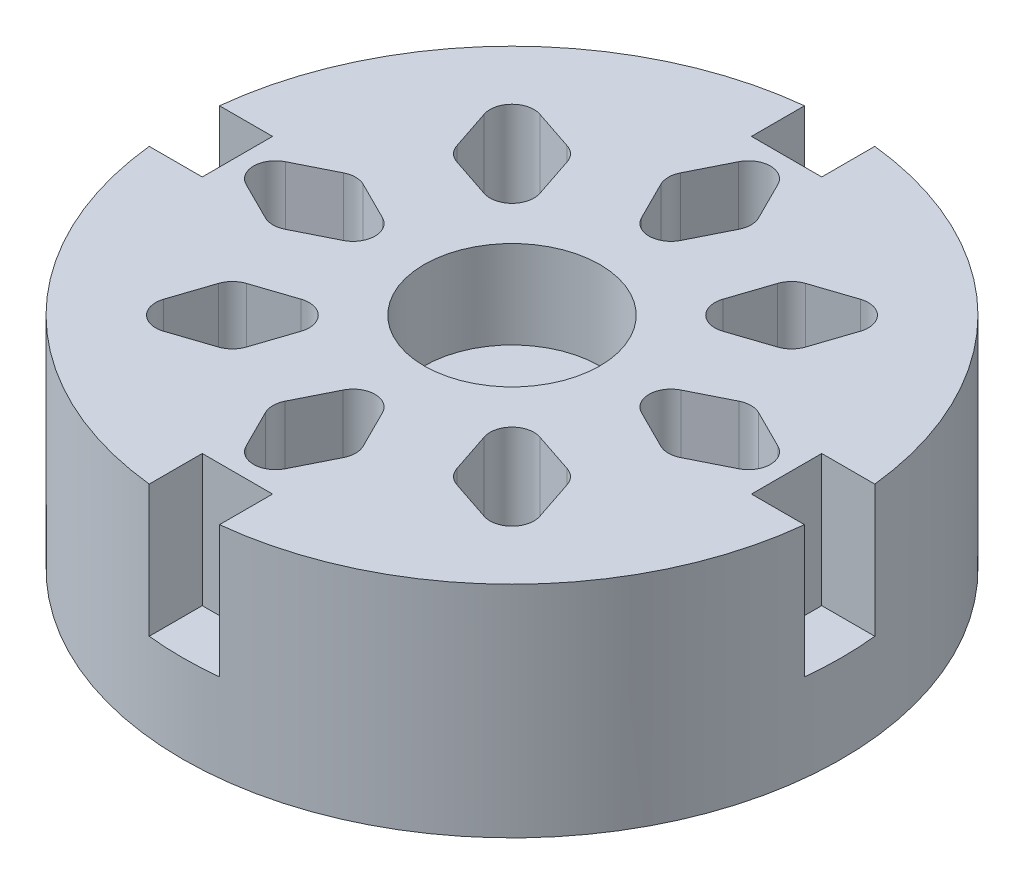
SolidWorks part; units mm, degrees
material "PET"
ref_plane "Спереди" through (0, 0, 0) normal (0, 0, 1) x (1, 0, 0)
ref_plane "Сверху" through (0, 0, 0) normal (0, 1, 0) x (1, 0, 0)
ref_plane "Справа" through (0, 0, 0) normal (1, 0, 0) x (0, 0, -1)
sketch "Эскиз1" plane through (0, 0, 0) normal (0, 1, 0) x (1, 0, 0)
  circle A0 centre (0, 0) radius 4
  circle A1 centre (0, 0) radius 15
  dimension "D1" = 8
  dimension "D2" = 30
extrude "Бобышка-Вытянуть1" add sketch "Эскиз1" along normal blind 10
sketch "Эскиз4" plane through (0, 0, 0) normal (0, -1, 0) x (1, 0, 0)
  circle A16 centre (0, 0) radius 15
  circle A32 centre (0, 0) radius 15
  dimension "D1" = 0
extrude "Бобышка-Вытянуть2" add sketch "Эскиз4" against normal blind 6
sketch "Эскиз5" plane through (0, 6, 0) normal (0, 1, 0) x (1, 0, 0)
  circle A0 centre (0, 0) radius 1.6
  dimension "D1" = 3.2
extrude "Вырез-Вытянуть2" cut sketch "Эскиз5" against normal through all both and the other way through all
sketch "Эскиз6" plane through (0, 0, 0) normal (0, -1, 0) x (1, 0, 0)
  line L0 (0, 0) -> (-5, 0) construction
  line L1 (-6.7889, 0.8944) -> (-8.5528, 1.7764)
  line L2 (-9.4472, 1.7764) -> (-11.2111, 0.8944)
  line L3 (-11.2111, -0.8944) -> (-9.4472, -1.7764)
  line L4 (-8.5528, -1.7764) -> (-6.7889, -0.8944)
  line L5 (-13, 0) -> (-5, 0) construction
  line L6 (-9, 2) -> (-9, -2) construction
  line L7 (-4.168, 5.4329) -> (-4.7916, 7.3038)
  line L8 (-5.4241, 7.9363) -> (-7.295, 8.5599)
  line L9 (-8.5599, 7.295) -> (-7.9363, 5.4241)
  line L10 (-7.3038, 4.7916) -> (-5.4329, 4.168)
  line L11 (0, 0) -> (-3.5355, 3.5355) construction
  line L12 (-9.1924, 9.1924) -> (-3.5355, 3.5355) construction
  line L13 (-4.9497, 7.7782) -> (-7.7782, 4.9497) construction
  line L14 (0.8944, 6.7889) -> (1.7764, 8.5528)
  line L15 (1.7764, 9.4472) -> (0.8944, 11.2111)
  line L16 (-0.8944, 11.2111) -> (-1.7764, 9.4472)
  line L17 (-1.7764, 8.5528) -> (-0.8944, 6.7889)
  line L18 (0, 0) -> (0, 5) construction
  line L19 (0, 13) -> (0, 5) construction
  line L20 (2, 9) -> (-2, 9) construction
  line L21 (5.4329, 4.168) -> (7.3038, 4.7916)
  line L22 (7.9363, 5.4241) -> (8.5599, 7.295)
  line L23 (7.295, 8.5599) -> (5.4241, 7.9363)
  line L24 (4.7916, 7.3038) -> (4.168, 5.4329)
  line L25 (0, 0) -> (3.5355, 3.5355) construction
  line L26 (9.1924, 9.1924) -> (3.5355, 3.5355) construction
  line L27 (7.7782, 4.9497) -> (4.9497, 7.7782) construction
  line L28 (6.7889, -0.8944) -> (8.5528, -1.7764)
  line L29 (9.4472, -1.7764) -> (11.2111, -0.8944)
  line L30 (11.2111, 0.8944) -> (9.4472, 1.7764)
  line L31 (8.5528, 1.7764) -> (6.7889, 0.8944)
  line L32 (0, 0) -> (5, 0) construction
  line L33 (13, 0) -> (5, 0) construction
  line L34 (9, -2) -> (9, 2) construction
  line L35 (4.168, -5.4329) -> (4.7916, -7.3038)
  line L36 (5.4241, -7.9363) -> (7.295, -8.5599)
  line L37 (8.5599, -7.295) -> (7.9363, -5.4241)
  line L38 (7.3038, -4.7916) -> (5.4329, -4.168)
  line L39 (0, 0) -> (3.5355, -3.5355) construction
  line L40 (9.1924, -9.1924) -> (3.5355, -3.5355) construction
  line L41 (4.9497, -7.7782) -> (7.7782, -4.9497) construction
  line L42 (-0.8944, -6.7889) -> (-1.7764, -8.5528)
  line L43 (-1.7764, -9.4472) -> (-0.8944, -11.2111)
  line L44 (0.8944, -11.2111) -> (1.7764, -9.4472)
  line L45 (1.7764, -8.5528) -> (0.8944, -6.7889)
  line L46 (0, 0) -> (0, -5) construction
  line L47 (0, -13) -> (0, -5) construction
  line L48 (-2, -9) -> (2, -9) construction
  line L49 (-5.4329, -4.168) -> (-7.3038, -4.7916)
  line L50 (-7.9363, -5.4241) -> (-8.5599, -7.295)
  line L51 (-7.295, -8.5599) -> (-5.4241, -7.9363)
  line L52 (-4.7916, -7.3038) -> (-4.168, -5.4329)
  line L53 (0, 0) -> (-3.5355, -3.5355) construction
  line L54 (-9.1924, -9.1924) -> (-3.5355, -3.5355) construction
  line L55 (-7.7782, -4.9497) -> (-4.9497, -7.7782) construction
  arc A0 (-9.4472, -1.7764) -> (-8.5528, -1.7764) centre (-9, -0.882) ccw
  arc A1 (-6.7889, -0.8944) -> (-6.7889, 0.8944) centre (-7.2361, 0) ccw
  arc A2 (-8.5528, 1.7764) -> (-9.4472, 1.7764) centre (-9, 0.882) ccw
  arc A3 (-11.2111, 0.8944) -> (-11.2111, -0.8944) centre (-10.7639, 0) ccw
  arc A4 (-7.9363, 5.4241) -> (-7.3038, 4.7916) centre (-6.9876, 5.7403) ccw
  arc A5 (-5.4329, 4.168) -> (-4.168, 5.4329) centre (-5.1167, 5.1167) ccw
  arc A6 (-4.7916, 7.3038) -> (-5.4241, 7.9363) centre (-5.7403, 6.9876) ccw
  arc A7 (-7.295, 8.5599) -> (-8.5599, 7.295) centre (-7.6112, 7.6112) ccw
  arc A8 (-1.7764, 9.4472) -> (-1.7764, 8.5528) centre (-0.882, 9) ccw
  arc A9 (-0.8944, 6.7889) -> (0.8944, 6.7889) centre (0, 7.2361) ccw
  arc A10 (1.7764, 8.5528) -> (1.7764, 9.4472) centre (0.882, 9) ccw
  arc A11 (0.8944, 11.2111) -> (-0.8944, 11.2111) centre (0, 10.7639) ccw
  arc A12 (5.4241, 7.9363) -> (4.7916, 7.3038) centre (5.7403, 6.9876) ccw
  arc A13 (4.168, 5.4329) -> (5.4329, 4.168) centre (5.1167, 5.1167) ccw
  arc A14 (7.3038, 4.7916) -> (7.9363, 5.4241) centre (6.9876, 5.7403) ccw
  arc A15 (8.5599, 7.295) -> (7.295, 8.5599) centre (7.6112, 7.6112) ccw
  arc A16 (9.4472, 1.7764) -> (8.5528, 1.7764) centre (9, 0.882) ccw
  arc A17 (6.7889, 0.8944) -> (6.7889, -0.8944) centre (7.2361, 0) ccw
  arc A18 (8.5528, -1.7764) -> (9.4472, -1.7764) centre (9, -0.882) ccw
  arc A19 (11.2111, -0.8944) -> (11.2111, 0.8944) centre (10.7639, 0) ccw
  arc A20 (7.9363, -5.4241) -> (7.3038, -4.7916) centre (6.9876, -5.7403) ccw
  arc A21 (5.4329, -4.168) -> (4.168, -5.4329) centre (5.1167, -5.1167) ccw
  arc A22 (4.7916, -7.3038) -> (5.4241, -7.9363) centre (5.7403, -6.9876) ccw
  arc A23 (7.295, -8.5599) -> (8.5599, -7.295) centre (7.6112, -7.6112) ccw
  arc A24 (1.7764, -9.4472) -> (1.7764, -8.5528) centre (0.882, -9) ccw
  arc A25 (0.8944, -6.7889) -> (-0.8944, -6.7889) centre (0, -7.2361) ccw
  arc A26 (-1.7764, -8.5528) -> (-1.7764, -9.4472) centre (-0.882, -9) ccw
  arc A27 (-0.8944, -11.2111) -> (0.8944, -11.2111) centre (0, -10.7639) ccw
  arc A28 (-5.4241, -7.9363) -> (-4.7916, -7.3038) centre (-5.7403, -6.9876) ccw
  arc A29 (-4.168, -5.4329) -> (-5.4329, -4.168) centre (-5.1167, -5.1167) ccw
  arc A30 (-7.3038, -4.7916) -> (-7.9363, -5.4241) centre (-6.9876, -5.7403) ccw
  arc A31 (-8.5599, -7.295) -> (-7.295, -8.5599) centre (-7.6112, -7.6112) ccw
  point P3 (-9, 0)
  point P21 (0, -9)
  point P23 (-6.364, 6.364)
  point P40 (0, 9)
  point P57 (6.364, 6.364)
  point P74 (9, 0)
  point P91 (6.364, -6.364)
  point P107 (0, 0)
  point P123 (-6.364, -6.364)
  dimension "D4" = 1
  dimension "D1" = 4
  dimension "D2" = 8
  dimension "D3" = 5
  dimension "D5" = 8
extrude "Вырез-Вытянуть3" cut sketch "Эскиз6" against normal through all both and the other way through all
sketch "Эскиз8" plane through (0, 10, 0) normal (0, 1, 0) x (1, 0, 0)
  line L0 (0, 0) -> (-15, 0) construction
  line L1 (1.6, 12.5) -> (1.6, 17.5)
  line L2 (-12.5, 1.6) -> (-17.5, 1.6)
  line L3 (-12.5, 1.6) -> (-12.5, -1.6)
  line L4 (-12.5, -1.6) -> (-17.5, -1.6)
  line L5 (-17.5, 1.6) -> (-17.5, -1.6)
  line L6 (-12.5, 1.6) -> (-17.5, -1.6) construction
  line L7 (-12.5, -1.6) -> (-17.5, 1.6) construction
  line L8 (1.6, 12.5) -> (-1.6, 12.5)
  line L9 (-1.6, 12.5) -> (-1.6, 17.5)
  line L10 (1.6, 17.5) -> (-1.6, 17.5)
  line L11 (0, 0) -> (0, 15) construction
  line L12 (1.6, 12.5) -> (-1.6, 17.5) construction
  line L13 (-1.6, 12.5) -> (1.6, 17.5) construction
  line L14 (12.5, -1.6) -> (17.5, -1.6)
  line L15 (12.5, -1.6) -> (12.5, 1.6)
  line L16 (12.5, 1.6) -> (17.5, 1.6)
  line L17 (17.5, -1.6) -> (17.5, 1.6)
  line L18 (0, 0) -> (15, 0) construction
  line L19 (12.5, -1.6) -> (17.5, 1.6) construction
  line L20 (12.5, 1.6) -> (17.5, -1.6) construction
  line L21 (-1.6, -12.5) -> (-1.6, -17.5)
  line L22 (-1.6, -12.5) -> (1.6, -12.5)
  line L23 (1.6, -12.5) -> (1.6, -17.5)
  line L24 (-1.6, -17.5) -> (1.6, -17.5)
  line L25 (0, 0) -> (0, -15) construction
  line L26 (-1.6, -12.5) -> (1.6, -17.5) construction
  line L27 (1.6, -12.5) -> (-1.6, -17.5) construction
  circle A0 centre (0, 0) radius 15 construction
  point P28 (0, 0)
  dimension "D1" = 3.2
  dimension "D2" = 5
  dimension "D3" = 4
extrude "Вырез-Вытянуть4" cut sketch "Эскиз8" against normal blind 6
sketch "Эскиз9" plane through (0, 0, 0) normal (0, -1, 0) x (1, 0, 0)
  circle A0 centre (0, 0) radius 3
  dimension "D1" = 6
extrude "Вырез-Вытянуть5" cut sketch "Эскиз9" against normal blind 2
